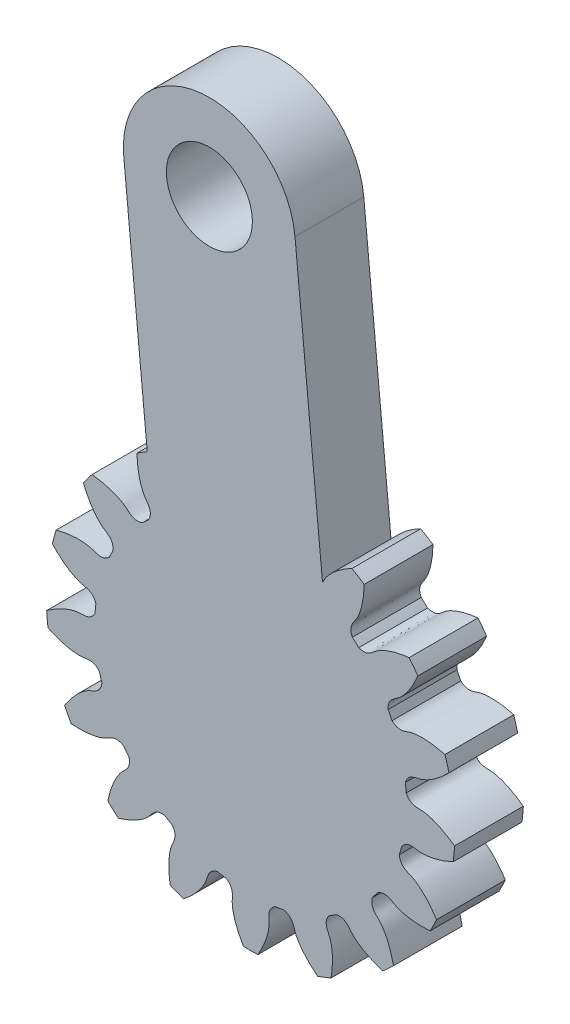
SolidWorks part; units mm, degrees
ref_plane "前视基准面" through (0, 0, 0) normal (0, 0, 1) x (1, 0, 0)
ref_plane "上视基准面" through (0, 0, 0) normal (0, 1, 0) x (1, 0, 0)
ref_plane "右视基准面" through (0, 0, 0) normal (1, 0, 0) x (0, 0, -1)
sketch "草图1" plane through (0, 0, 0) normal (0, 0, 1) x (1, 0, 0)
  circle A0 centre (0, 0) radius 11.875
extrude "凸台-拉伸1" add sketch "草图1" along normal blind 4
ref_axis "基准轴1" through (0, 0, -0.1) along (0, 0, 1)
sketch "草图2" plane through (0, 0, 0) normal (0, 0, 1) x (1, 0, 0)
  line L0 (0, 0) -> (0, 11.875) construction
  circle A0 centre (0, 0) radius 11.875 construction
  arc A1 (0.2521, 9.059) -> (-0.2521, 9.059) centre (0, 0) ccw
  arc A2 (3.8946, 13.4259) -> (-3.8946, 13.4259) centre (0, 0) ccw
  spline S0 degree 3 poles (0.2521, 9.059) (0.7848, 9.281) (0.7077, 9.6935) (0.7979, 10.081) (0.8062, 10.1139) (0.8163, 10.1505) (0.8282, 10.1907) (0.8421, 10.2345) (0.8582, 10.2818) (0.8766, 10.3324) (0.8974, 10.3865) (0.9208, 10.4438) (0.947, 10.5043) (0.976, 10.5679) (1.008, 10.6345) (1.0431, 10.704) (1.0815, 10.7763) (1.1232, 10.8513) (1.1685, 10.929) (1.2174, 11.0091) (1.27, 11.0916) (1.3265, 11.1763) (1.3869, 11.2632) (1.4514, 11.3521) (1.5201, 11.4429) (1.5931, 11.5354) (1.6704, 11.6295) (1.7522, 11.7251) (1.8386, 11.822) (1.9295, 11.9201) (2.0252, 12.0192) (2.1257, 12.1193) (2.2311, 12.22) (2.3414, 12.3213) (2.4567, 12.4231) (2.577, 12.5251) (2.7025, 12.6272) (2.8331, 12.7292) (2.969, 12.831) (3.1101, 12.9323) (3.2564, 13.0331) (3.4081, 13.1332) (3.6198, 13.2668) (3.7832, 13.3632) (3.8946, 13.4259) knots 0 0 0 0 0.193883 0.199024 0.204851 0.211363 0.21856 0.226443 0.235011 0.244265 0.254205 0.264829 0.27614 0.288136 0.300817 0.314184 0.328236 0.342973 0.358397 0.374505 0.391299 0.408779 0.426944 0.445795 0.465331 0.485552 0.506459 0.528051 0.550329 0.573293 0.596941 0.621276 0.646296 0.672001 0.698392 0.725468 0.753229 0.781677 0.810809 0.840627 0.871131 0.90232 0.934195 1 1 1 1
  spline S1 degree 3 poles (-0.2521, 9.059) (-0.7848, 9.281) (-0.7077, 9.6935) (-0.7979, 10.081) (-0.8062, 10.1139) (-0.8163, 10.1505) (-0.8282, 10.1907) (-0.8421, 10.2345) (-0.8582, 10.2818) (-0.8766, 10.3324) (-0.8974, 10.3865) (-0.9208, 10.4438) (-0.947, 10.5043) (-0.976, 10.5679) (-1.008, 10.6345) (-1.0431, 10.704) (-1.0815, 10.7763) (-1.1232, 10.8513) (-1.1685, 10.929) (-1.2174, 11.0091) (-1.27, 11.0916) (-1.3265, 11.1763) (-1.3869, 11.2632) (-1.4514, 11.3521) (-1.5201, 11.4429) (-1.5931, 11.5354) (-1.6704, 11.6295) (-1.7522, 11.7251) (-1.8386, 11.822) (-1.9295, 11.9201) (-2.0252, 12.0192) (-2.1257, 12.1193) (-2.2311, 12.22) (-2.3414, 12.3213) (-2.4567, 12.4231) (-2.577, 12.5251) (-2.7025, 12.6272) (-2.8331, 12.7292) (-2.969, 12.831) (-3.1101, 12.9323) (-3.2564, 13.0331) (-3.4081, 13.1332) (-3.6198, 13.2668) (-3.7832, 13.3632) (-3.8946, 13.4259) knots 0 0 0 0 0.193883 0.199024 0.204851 0.211363 0.21856 0.226443 0.235011 0.244265 0.254205 0.264829 0.27614 0.288136 0.300817 0.314184 0.328236 0.342973 0.358397 0.374505 0.391299 0.408779 0.426944 0.445795 0.465331 0.485552 0.506459 0.528051 0.550329 0.573293 0.596941 0.621276 0.646296 0.672001 0.698392 0.725468 0.753229 0.781677 0.810809 0.840627 0.871131 0.90232 0.934195 1 1 1 1
extrude "切除-拉伸1" cut sketch "草图2" along normal through all
pattern_circular "阵列(圆周)1" count 17 every 21.176 about axis through (0, 0, -0.1) along (0, 0, 1) of "切除-拉伸1"
sketch "草图3" plane through (0, 0, 0) normal (0, 0, 1) x (1, 0, 0)
  circle A0 centre (0, 0) radius 10.625 construction
  dimension "Dn" = 21.25
sketch "草图4" plane through (0, 0, 4) normal (0, 0, 1) x (1, 0, 0)
  line L0 (0, 0) -> (-2.3961, 24.8849) construction
  line L1 (-4.977, -0.4792) -> (-7.3731, 24.4057)
  line L2 (4.977, 0.4792) -> (2.5808, 25.3641)
  line L3 (0, 0) -> (0, 14.4862) construction
  arc A0 (-4.977, -0.4792) -> (4.977, 0.4792) centre (0, 0) ccw
  arc A1 (2.5808, 25.3641) -> (-7.3731, 24.4057) centre (-2.3961, 24.8849) ccw
  circle A2 centre (-2.3961, 24.8849) radius 2.5
  point P3 (-1.1981, 12.4425)
  dimension "D4" = 5
  dimension "D1" = 25
  dimension "D2" = 10
  dimension "D3" = 5.5
extrude "凸台-拉伸2" add sketch "草图4" against normal blind 4
